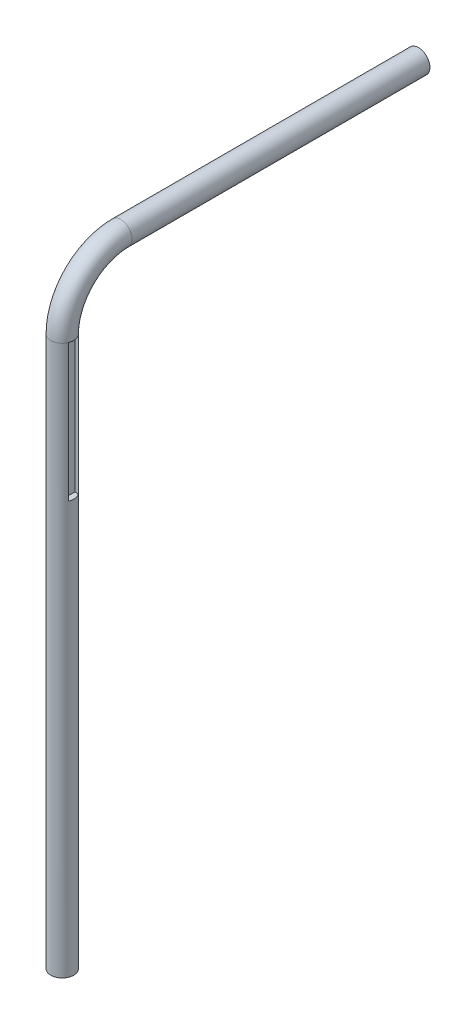
SolidWorks part; units mm, degrees
material "Cast Carbon Steel"
ref_plane "Front Plane" through (0, 0, 0) normal (0, 0, 1) x (1, 0, 0)
ref_plane "Top Plane" through (0, 0, 0) normal (0, 1, 0) x (1, 0, 0)
ref_plane "Right Plane" through (0, 0, 0) normal (1, 0, 0) x (0, 0, -1)
sketch "Sketch2" plane through (0, 0, 0) normal (1, 0, 0) x (0, 0, -1)
  arc A0 (-64.8338, 0) -> (0, 64.8338) centre (0, 0) cw
sketch "Sketch3" plane through (0, 0, 0) normal (0, 1, 0) x (1, 0, 0)
  circle A0 centre (0, -64.8338) radius 12.7
  circle A1 centre (0, -64.8338) radius 4.7625
  dimension "D1" = 25.4
  dimension "D2" = 7.9375
sweep "Sweep1" add profiles "Sketch3" path "Sketch2"
ref_plane "Plane1" through (0, 0, 0) normal (0, -1, 0) x (-1, 0, 0)
ref_plane "Plane2" through (0, 0, 0) normal (0, 0, -1) x (-1, 0, 0)
sketch "Sketch4" plane through (0, 0, 0) normal (0, -1, 0) x (-1, 0, 0)
  circle A0 centre (0, -64.8338) radius 12.7
  circle A1 centre (0, -64.8338) radius 4.7625
  dimension "D1" = 7.9375
  dimension "D2" = 25.4
extrude "Boss-Extrude3" add sketch "Sketch4" along normal blind 609.6
sketch "Sketch5" plane through (0, 0, 0) normal (0, 0, -1) x (-1, 0, 0)
  circle A0 centre (0, 64.8338) radius 12.7
  circle A1 centre (0, 64.8338) radius 4.7625
  dimension "D1" = 7.9375
  dimension "D2" = 25.4
extrude "Boss-Extrude4" add sketch "Sketch5" along normal blind 330.2
ref_plane "Plane3" through (-12.7, 0, 0) normal (-1, 0, 0) x (0, 0, 1)
ref_plane "Plane4" through (12.7, 0, 0) normal (1, 0, 0) x (0, 0, -1)
sketch "Sketch7" plane through (12.7, 0, 0) normal (1, 0, 0) x (0, 0, -1)
  line L0 (0, -13.97) -> (0, 13.97) construction
  line L1 (-69.85, 0) -> (-57.15, 0)
  line L2 (-69.85, 0) -> (-69.85, -152.4)
  line L3 (-69.85, -152.4) -> (-57.15, -152.4)
  line L4 (-57.15, 0) -> (-57.15, -152.4)
  line L5 (-52.1338, 0) -> (-77.5338, 0) construction
  point P9 (-63.5, -152.4)
  dimension "D1" = 12.7
  dimension "D2" = 152.4
  dimension "D3" = 57.15
  dimension "D4" = 63.5
extrude "Cut-Extrude2" cut sketch "Sketch7" against normal blind 6.35
